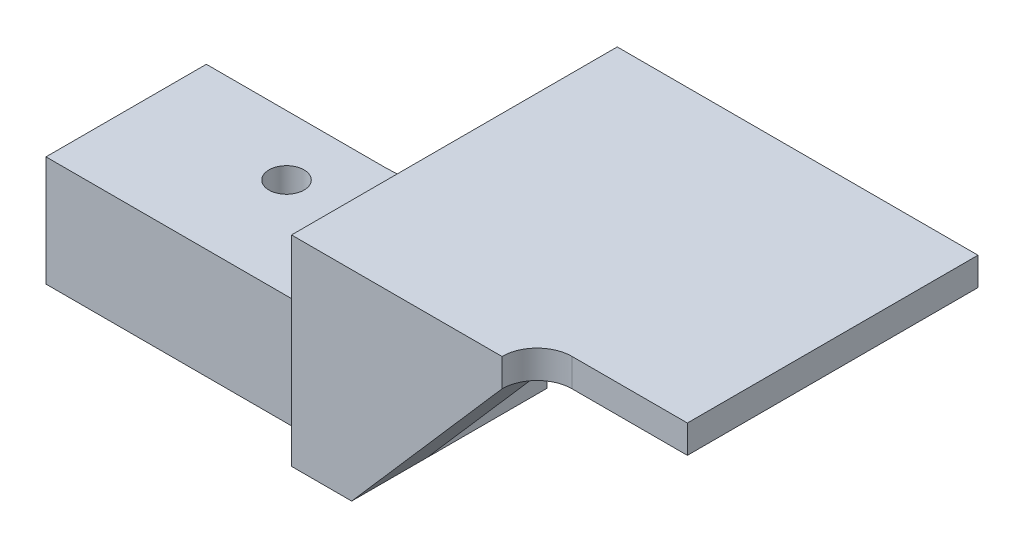
SolidWorks part; units mm, degrees
material "黄铜"
ref_plane "前视基准面" through (0, 0, 0) normal (0, 0, 1) x (1, 0, 0)
ref_plane "上视基准面" through (0, 0, 0) normal (0, 1, 0) x (1, 0, 0)
ref_plane "右视基准面" through (0, 0, 0) normal (1, 0, 0) x (0, 0, -1)
sketch "草图1" plane through (0, 0, 0) normal (0, 1, 0) x (1, 0, 0)
  line L1 (0, 0) -> (34, 0)
  line L2 (0, 0) -> (0, -16)
  line L3 (0, -16) -> (34, -16)
  line L4 (34, 0) -> (34, -16)
  dimension "D1" = 34
  dimension "D2" = 16
extrude "凸台-拉伸1" add sketch "草图1" along normal blind 11
sketch "草图2" plane through (0, 0, 0) normal (0, 0, -1) x (-1, 0, 0)
  line L0 (0, 11) -> (0, 0) construction
  line L1 (0, 7.1) -> (-34, 7.1)
  line L2 (0, 7.1) -> (0, 3.9)
  line L3 (0, 3.9) -> (-34, 3.9)
  line L4 (-34, 7.1) -> (-34, 3.9)
  line L5 (-34, 11) -> (-34, 0) construction
  line L6 (-34, 0) -> (0, 0) construction
  line L7 (-34, 11) -> (0, 11) construction
  dimension "D1" = 3.9
  dimension "D2" = 3.9
extrude "切除-拉伸1" cut sketch "草图2" against normal blind 12
sketch "草图3" plane through (0, 11, 0) normal (0, 1, 0) x (1, 0, 0)
  line L0 (0, -12) -> (34, -12) construction
  line L1 (0, 0) -> (34, 0)
  line L2 (0, 0) -> (0, -12)
  line L3 (0, -12) -> (34, -12)
  line L4 (34, 0) -> (34, -12)
  line L5 (34, -16) -> (34, 0) construction
  point P9 (14, -6)
  dimension "D1" = 6
  dimension "D2" = 14
sketch "草图4" plane through (0, 11, 0) normal (0, 1, 0) x (1, 0, 0)
  point P0 (14, -6)
hole_wizard "孔1" positions "草图4" profile "草图5" legacy end condition through all
sketch "草图5" plane through (14, 11, 6) normal (1, 0, 0) x (0, 0, 1)
  line L0 (0, 0) -> (0, 11)
  line L1 (0, 11) -> (1.75, 11)
  line L2 (1.75, 11) -> (1.75, 0)
  line L3 (1.75, 0) -> (0, 0)
  line L4 (0, 110) -> (0, -10) construction
  dimension "直径" = 3.5
  dimension "深度" = 11
sketch "草图6" plane through (0, 0, 0) normal (0, 0, -1) x (-1, 0, 0)
  line L0 (0, 7.1) -> (-34, 7.1) construction
  line L1 (-34, 11) -> (-28, 11)
  line L2 (-34, 11) -> (-34, 7.1)
  line L3 (-34, 7.1) -> (-28, 7.1)
  line L4 (-28, 11) -> (-28, 7.1)
  dimension "D1" = 6
extrude "凸台-拉伸2" add sketch "草图6" along normal blind 13
fillet "圆角1" radius 10 1 edges at (28, 9.05, 0)
sketch "草图7" plane through (0, 11, 0) normal (0, 1, 0) x (1, 0, 0)
  line L0 (0, -16) -> (34, -16) construction
  line L1 (34, 13) -> (28, 13)
  line L2 (34, 13) -> (34, -16)
  line L3 (34, -16) -> (28, -16)
  line L4 (28, 13) -> (28, -16)
  line L5 (28, 13) -> (28, 10) construction
extrude "凸台-拉伸3" add sketch "草图7" along normal blind 9
sketch "草图8" plane through (34, 0, 0) normal (1, 0, 0) x (0, 0, -1)
  line L0 (-16, 20) -> (-16, 0) construction
  line L1 (13, 20) -> (-16, 20)
  line L2 (13, 20) -> (13, 17.2)
  line L3 (13, 17.2) -> (-16, 17.2)
  line L4 (-16, 20) -> (-16, 17.2)
  dimension "D1" = 2.8
extrude "凸台-拉伸4" add sketch "草图8" along normal blind 30
sketch "草图10" plane through (0, 0, 16) normal (0, 0, 1) x (1, 0, 0)
  line L0 (34, 0) -> (49, 17.2)
  line L1 (64, 17.2) -> (34, 17.2) construction
  line L2 (34, 0) -> (34, 17.2)
  line L3 (34, 17.2) -> (49, 17.2)
  line L4 (49, 17.2) -> (49, 20)
  line L5 (28, 20) -> (64, 20) construction
  line L6 (49, 20) -> (28, 20)
  line L7 (28, 20) -> (28, 0)
  line L8 (0, 0) -> (34, 0) construction
  line L9 (28, 0) -> (34, 0)
  line L10 (49, 17.2) -> (49, 20)
  line M2 (0, 0) -> (34, 0)
  line M3 (34, 0) -> (34, 17.2)
  line M4 (34, 17.2) -> (64, 17.2)
  line M6 (64, 20) -> (28, 20)
  line M7 (28, 20) -> (28, 11)
  dimension "D1" = 15
extrude "凸台-拉伸6" add sketch "草图10" along normal blind 3.5 contours L7 L4 M7 M2 M3 M4 M6 | L0 M3 M4 region at (39, 11.4667, 16) region at (33.7222, 12.2296, 16)
fillet "圆角2" radius 1 4 edges at (28, 7.1, -11.5) (25.0711, 7.1, -2.9289) (9, 7.1, 0) (17, 3.9, 0)
fillet "圆角3" radius 3.5 1 edges at (28, 5.5, 16)
fillet "圆角4" radius 3.5 1 edges at (49, 18.6, 16)
sketch "草图11" plane through (0, 0, 16) normal (0, 0, -1) x (-1, 0, 0)
  line L0 (-49, 17.2) -> (-34, 17.2)
  line L1 (-64, 17.2) -> (-34, 17.2) construction
  line L2 (-34, 17.2) -> (-34, 0)
  line L3 (-34, 0) -> (-49, 17.2)
extrude "凸台-拉伸7" add sketch "草图11" along normal blind 4
sketch "草图12" plane through (0, 0, -13) normal (0, 0, -1) x (-1, 0, 0)
  line L0 (-34, 17.2) -> (-49, 17.2) construction
  line L1 (-34, 7.1) -> (-33.8, 7.1)
  line L2 (-34, 7.1) -> (-34, 17.2)
  line L3 (-34, 17.2) -> (-33.8, 17.2)
  line L4 (-33.8, 7.1) -> (-33.8, 17.2)
  dimension "D1" = 0.2
extrude "切除-拉伸2" cut sketch "草图12" against normal blind 25
